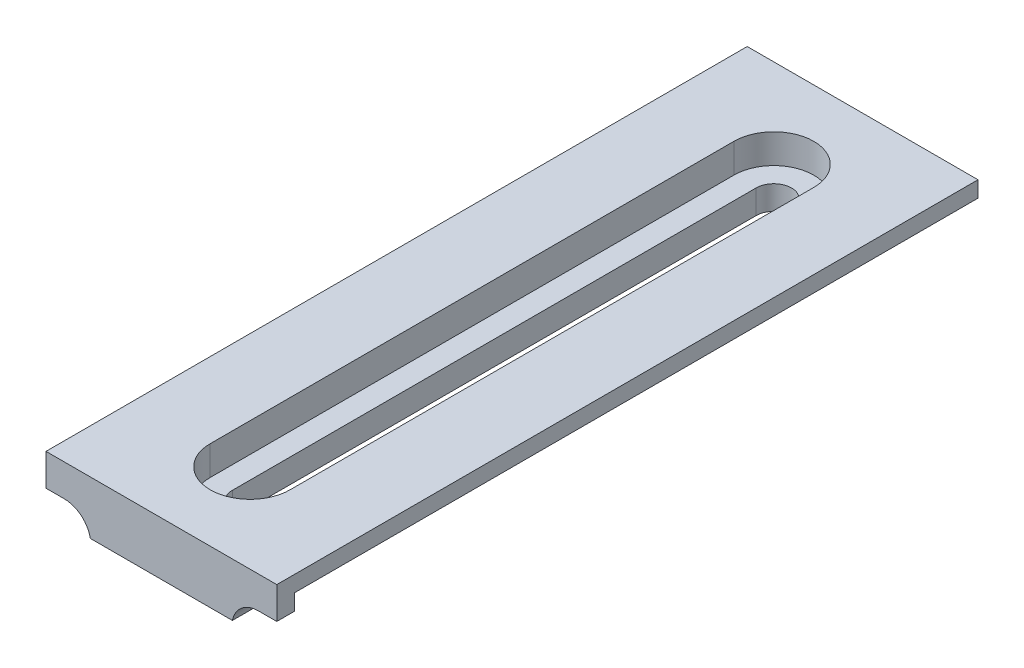
SolidWorks part; units mm, degrees
ref_plane "Płaszczyzna przednia" through (0, 0, 0) normal (0, 0, 1) x (1, 0, 0)
ref_plane "Płaszczyzna górna" through (0, 0, 0) normal (0, 1, 0) x (1, 0, 0)
ref_plane "Płaszczyzna prawa" through (0, 0, 0) normal (1, 0, 0) x (0, 0, -1)
sketch "Szkic1" plane through (0, 0, 0) normal (0, 0, 1) x (1, 0, 0)
  line L0 (-13, 0) -> (-13, 1.8)
  line L1 (-13, 1.8) -> (13, 1.8)
  line L2 (13, 1.8) -> (13, 0)
  line L3 (13, 0) -> (8, 0)
  line L4 (8, 0) -> (8, -4.2)
  line L5 (8, -4.2) -> (-8, -4.2)
  line L6 (-8, -4.2) -> (-8, 0)
  line L7 (-8, 0) -> (-13, 0)
  line L8 (0, 0) -> (0, 9.8508) construction
  point P11 (-10.5, 0)
  dimension "D1" = 26
  dimension "D2" = 16
  dimension "D3" = 6
  dimension "D4" = 1.8
extrude "Dodanie-wyciągnięcie1" add sketch "Szkic1" along normal blind 79
sketch "Szkic3" plane through (0, -4.2, 0) normal (0, -1, 0) x (1, 0, 0)
  line L0 (0, 69) -> (0, 10) construction
  line L1 (2, 69) -> (2, 10)
  line L2 (-2, 69) -> (-2, 10)
  line L3 (-8, 79) -> (8, 79) construction
  line L4 (-8, 0) -> (8, 0) construction
  arc A0 (2, 69) -> (-2, 69) centre (0, 69) ccw
  arc A1 (-2, 10) -> (2, 10) centre (0, 10) ccw
  point P3 (0, 39.5)
  point P8 (0, 71)
  dimension "D2" = 10
  dimension "D3" = 10
  dimension "D1" = 2
extrude "Wytnij-wyciągnięcie1" cut sketch "Szkic3" against normal through all
sketch "Szkic4" plane through (0, 1.8, 0) normal (0, 1, 0) x (1, 0, 0)
  line L0 (0, -69) -> (0, -10) construction
  line L1 (-4.5, -69) -> (-4.5, -10)
  line L2 (4.5, -69) -> (4.5, -10)
  arc A0 (-4.5, -69) -> (4.5, -69) centre (0, -69) ccw
  arc A1 (4.5, -10) -> (-4.5, -10) centre (0, -10) ccw
  point P4 (0, -39.5)
  dimension "D1" = 9
extrude "Wytnij-wyciągnięcie2" cut sketch "Szkic4" against normal blind 3.3
sketch "Szkic5" plane through (0, 0, 79) normal (0, 0, 1) x (1, 0, 0)
  line L1 (13, -1.8) -> (-13, -1.8)
  line L2 (13, -1.8) -> (13, 1.8)
  line L3 (13, 1.8) -> (-13, 1.8)
  line L4 (-13, -1.8) -> (-13, 1.8)
  line L5 (13, -1.8) -> (-13, 1.8) construction
  line L6 (13, 1.8) -> (-13, -1.8) construction
  point P0 (0, 0)
extrude "Dodanie-wyciągnięcie2" add sketch "Szkic5" against normal blind 2
fillet "Zaokrąglenie3" radius 3 2 edges at (8, -1.8, 78) (-8, -1.8, 78)
